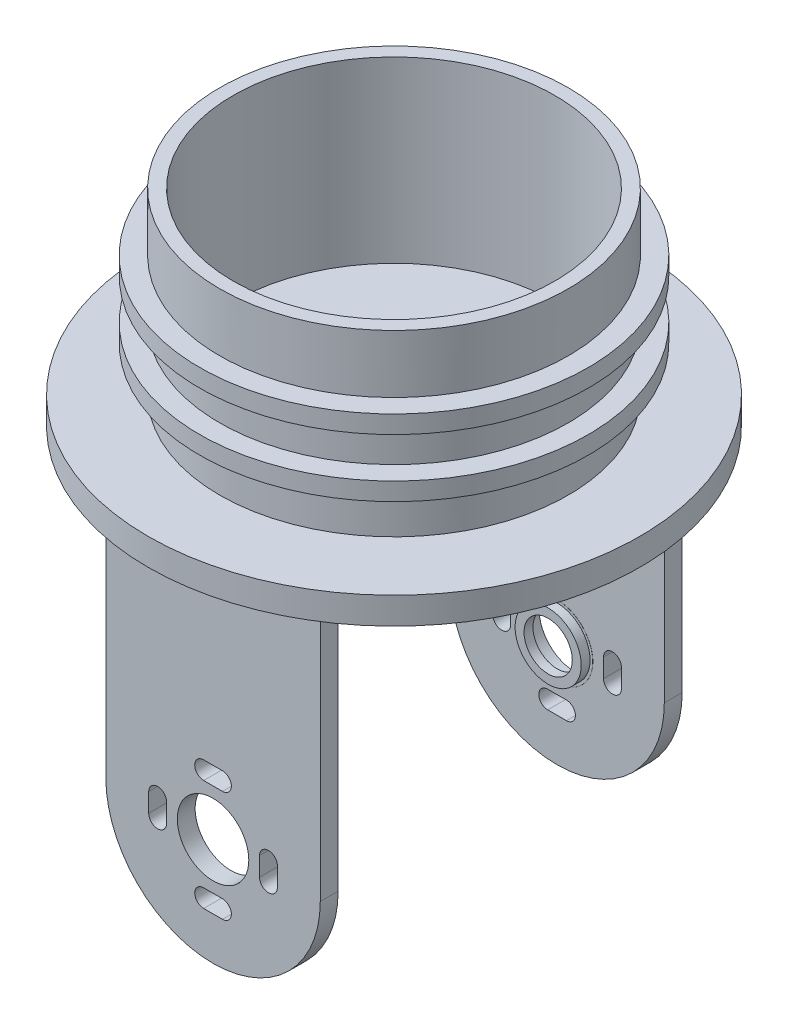
SolidWorks part; units mm, degrees
ref_plane "前基準面" through (0, 0, 0) normal (0, 0, 1) x (1, 0, 0)
ref_plane "上基準面" through (0, 0, 0) normal (0, 1, 0) x (1, 0, 0)
ref_plane "右基準面" through (0, 0, 0) normal (1, 0, 0) x (0, 0, -1)
sketch "草圖1" plane through (0, 0, 0) normal (0, 1, 0) x (1, 0, 0)
  circle A0 centre (0, 0) radius 19.5
  circle A1 centre (0, 0) radius 18
  dimension "D1" = 39
  dimension "D2" = 36
extrude "填料-伸長1" add sketch "草圖1" along normal blind 20
sketch "草圖3" plane through (0, 0, 0) normal (0, -1, 0) x (1, 0, 0)
  circle A0 centre (0, 0) radius 27.5
  dimension "D1" = 55
extrude "填料-伸長2" add sketch "草圖3" along normal blind 3
sketch "草圖4" plane through (0, 0, 0) normal (0, 0, 1) x (1, 0, 0)
  line L0 (0, 20) -> (0, -52.6673) construction
  line L1 (18, 20) -> (-18, 20) construction
  line L2 (-27.5, -3) -> (27.5, -3) construction
  line L3 (-10, -3) -> (10, -3)
  line L4 (-10, -3) -> (-10, -63)
  line L5 (-10, -63) -> (10, -63)
  line L6 (10, -3) -> (10, -63)
  line L8 (-6.5, -28) -> (6.5, -28)
  line L9 (-6.5, -28) -> (-6.5, -53)
  line L10 (-6.5, -53) -> (6.5, -53)
  line L11 (6.5, -28) -> (6.5, -53)
  dimension "D1" = 10
  dimension "D2" = 10
  dimension "D3" = 60
  dimension "D4" = 6.5
  dimension "D5" = 6.5
  dimension "D6" = 25
  dimension "D7" = 25
ref_plane "平面2" through (0, -3, 0) normal (0, -1, 0) x (-1, 0, 0)
ref_plane "平面5" through (0, 0, 0) normal (0, 1, 0) x (1, 0, 0)
ref_plane "平面6" through (0, 7, 0) normal (0, -1, 0) x (-1, 0, 0)
sketch "草圖25" plane through (0, 7, 0) normal (0, -1, 0) x (-1, 0, 0)
  circle A0 centre (0, 0) radius 21.75
  circle A1 centre (0, 0) radius 19.5
  dimension "D1" = 43.5
extrude "填料-伸長12" add sketch "草圖25" along normal blind 2
ref_plane "平面10" through (0, 10.5, 0) normal (0, -1, 0) x (-1, 0, 0)
sketch "草圖26" plane through (0, 10.5, 0) normal (0, -1, 0) x (-1, 0, 0)
  circle A0 centre (0, 0) radius 21.75
  circle A1 centre (0, 0) radius 19.5
extrude "填料-伸長13" add sketch "草圖26" against normal blind 2 from offset 1 offset against normal yes
ref_plane "平面11" through (0, -3, 0) normal (0, -1, 0) x (-1, 0, 0)
sketch "草圖27" plane through (0, -3, 0) normal (0, -1, 0) x (-1, 0, 0)
  line L0 (-27.5, 0) -> (27.5, 0) construction
  line L1 (-12, 20.25) -> (12, 20.25)
  line L2 (-12, 20.25) -> (-12, 18.25)
  line L3 (-12, 18.25) -> (12, 18.25)
  line L4 (12, 20.25) -> (12, 18.25)
  line L5 (-46.0389, 0) -> (46.0389, 0) construction
  line L6 (0, 0) -> (0, -33.56) construction
  line L7 (-12, -18.25) -> (12, -18.25)
  line L8 (12, -20.25) -> (12, -18.25)
  line L9 (-12, -20.25) -> (12, -20.25)
  line L10 (-12, -20.25) -> (-12, -18.25)
  circle A0 centre (0, 0) radius 27.5 construction
  point P13 (-12, 19.25)
  dimension "D1" = 18.25
  dimension "D2" = 24
  dimension "D3" = 12
  dimension "D4" = 2
ref_plane "平面12" through (0, 0, -18.25) normal (0, 0, 1) x (1, 0, 0)
sketch "草圖28" plane through (0, 0, -18.25) normal (0, 0, 1) x (1, 0, 0)
  line L0 (0, -3) -> (0, -48.9232) construction
  line L1 (12, -3) -> (-12, -3) construction
  line L2 (12, -3) -> (-12, -3) construction
  line L3 (-12, -3) -> (12, -3)
  line L4 (-12, -3) -> (-12, -33)
  line L6 (12, -3) -> (12, -33)
  line L7 (-12, -33) -> (12, -33) construction
  line L8 (-1.05, -26.8) -> (1.05, -26.8) construction
  line L9 (-1.05, -25.8) -> (1.05, -25.8)
  line L10 (-1.05, -27.8) -> (1.05, -27.8)
  line L11 (6.2, -31.95) -> (6.2, -34.05) construction
  line L12 (7.2, -31.95) -> (7.2, -34.05)
  line L13 (5.2, -31.95) -> (5.2, -34.05)
  line L14 (-1.05, -39.2) -> (1.05, -39.2) construction
  line L15 (-1.05, -40.2) -> (1.05, -40.2)
  line L16 (-1.05, -38.2) -> (1.05, -38.2)
  line L17 (-6.2, -31.95) -> (-6.2, -34.05) construction
  line L18 (-7.2, -31.95) -> (-7.2, -34.05)
  line L19 (-5.2, -31.95) -> (-5.2, -34.05)
  arc A1 (-12, -33) -> (12, -33) centre (0, -33) ccw
  circle A2 centre (0, -33) radius 4
  arc A3 (-1.05, -25.8) -> (-1.05, -27.8) centre (-1.05, -26.8) ccw
  arc A4 (1.05, -27.8) -> (1.05, -25.8) centre (1.05, -26.8) ccw
  arc A5 (7.2, -31.95) -> (5.2, -31.95) centre (6.2, -31.95) ccw
  arc A6 (5.2, -34.05) -> (7.2, -34.05) centre (6.2, -34.05) ccw
  arc A7 (-1.05, -40.2) -> (-1.05, -38.2) centre (-1.05, -39.2) cw
  arc A8 (1.05, -38.2) -> (1.05, -40.2) centre (1.05, -39.2) cw
  arc A9 (-7.2, -31.95) -> (-5.2, -31.95) centre (-6.2, -31.95) cw
  arc A10 (-5.2, -34.05) -> (-7.2, -34.05) centre (-6.2, -34.05) cw
  point P15 (0, -26.8)
  point P20 (6.2, -33)
  point P32 (0, -39.2)
  point P39 (-6.2, -33)
  dimension "D2" = 0
  dimension "D10" = 8
  dimension "D1" = 30
  dimension "D3" = 0
  dimension "D4" = 6.2
  dimension "D5" = 6.2
  dimension "D6" = 2.1
  dimension "D7" = 2
  dimension "D8" = 2.1
  dimension "D9" = 2
extrude "填料-伸長14" add sketch "草圖28" against normal blind 2
pattern_linear "直線複製排列1" count 2 spacing 38.5 along (0, 0, 1) of "填料-伸長14"
ref_plane "平面13" through (0, 0, 0) normal (0, 1, 0) x (1, 0, 0)
sketch "草圖30" plane through (0, 0, 0) normal (0, 1, 0) x (1, 0, 0)
  line L1 (-5.5, -8.9457) -> (5.5, -8.9457)
  line L2 (-5.5, -8.9457) -> (-5.5, -15.9457)
  line L3 (-5.5, -15.9457) -> (5.5, -15.9457)
  line L4 (5.5, -8.9457) -> (5.5, -15.9457)
sketch "草圖29" plane through (0, 0, 0) normal (0, 1, 0) x (1, 0, 0)
  line L0 (0, 18) -> (0, -18) construction
  line L2 (-4.5, -9.9457) -> (4.5, -9.9457)
  line L3 (-4.5, -9.9457) -> (-4.5, -14.9457)
  line L4 (-4.5, -14.9457) -> (4.5, -14.9457)
  line L5 (4.5, -9.9457) -> (4.5, -14.9457)
  circle A1 centre (0, 0) radius 18 construction
  circle A2 centre (0, 0) radius 18 construction
  dimension "D1" = 4.5
  dimension "D2" = 4.5
  dimension "D3" = 5
extrude "填料-伸長16" add sketch "草圖30" along normal blind 10
extrude "除料-伸長2" cut sketch "草圖29" against normal blind 10 and the other way blind 10
ref_plane "平面14" through (0, 0, -18.25) normal (0, 0, 1) x (1, 0, 0)
sketch "草圖31" plane through (0, 0, -18.25) normal (0, 0, 1) x (1, 0, 0)
  circle A0 centre (0, -33) radius 3.7
  circle A1 centre (0, -33) radius 2.7
  dimension "D1" = 7.4
  dimension "D2" = 5.4
extrude "填料-伸長17" add sketch "草圖31" along normal blind 1 separate body
sketch "草圖32" plane through (0, 0, -18.25) normal (0, 0, 1) x (1, 0, 0)
  circle A0 centre (0, -33) radius 3.7
  circle A1 centre (0, -33) radius 4
extrude "填料-伸長18" add sketch "草圖32" along normal blind 0.01
